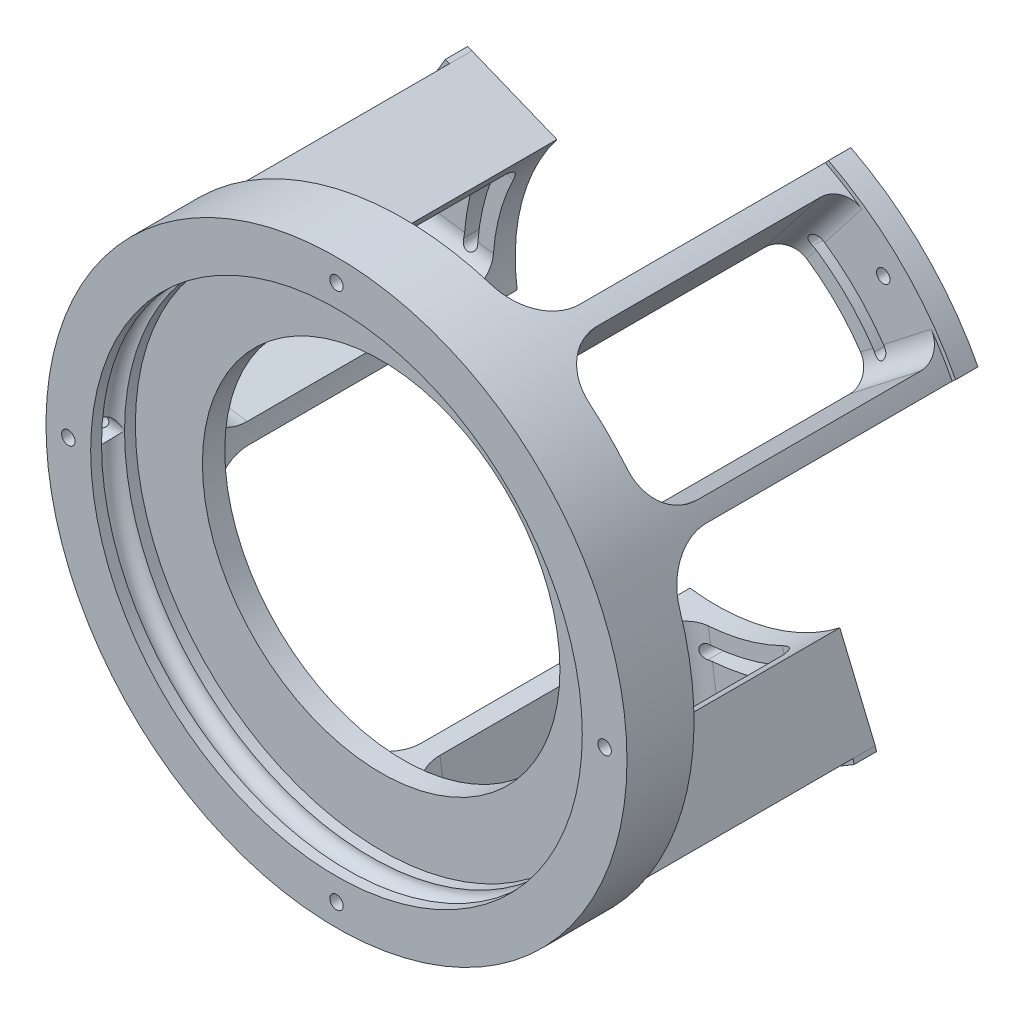
SolidWorks part; units mm, degrees
ref_plane "Alzado" through (0, 0, 0) normal (0, 0, 1) x (1, 0, 0)
ref_plane "Planta" through (0, 0, 0) normal (0, 1, 0) x (1, 0, 0)
ref_plane "Vista lateral" through (0, 0, 0) normal (1, 0, 0) x (0, 0, -1)
sketch "Croquis1" plane through (0, 0, 0) normal (0, 0, 1) x (1, 0, 0)
  circle A0 centre (0, 0) radius 65
  circle A1 centre (0, 0) radius 27.5
  dimension "D1" = 130
  dimension "D5" = 55
extrude "Saliente-Extruir1" add sketch "Croquis1" along normal blind 5
sketch "Croquis2" plane through (0, 0, 5) normal (0, 0, 1) x (1, 0, 0)
  circle A0 centre (0, 0) radius 65
  circle A1 centre (0, 0) radius 55
  dimension "D1" = 130
  dimension "D2" = 10
extrude "Saliente-Extruir2" add sketch "Croquis2" along normal blind 10
sketch "Croquis3" plane through (0, 0, 15) normal (0, 0, 1) x (1, 0, 0)
  line L0 (-73.6289, 0) -> (79.389, 0) construction
  line L1 (0, -78.8882) -> (0, 68.8706) construction
  circle A0 centre (-60, 0) radius 1.5
  circle A1 centre (0, 0) radius 55 construction
  circle A2 centre (0, 60) radius 1.5
  circle A3 centre (60, 0) radius 1.5
  circle A4 centre (0, -60) radius 1.5
  point P19 (0, 0)
  dimension "D1" = 3
  dimension "D2" = 60
  dimension "D3" = 4
extrude "Cortar-Extruir1" cut sketch "Croquis3" against normal blind 10
sketch "Croquis4" plane through (0, 0, 0) normal (0, 0, -1) x (-1, 0, 0)
  line L0 (0, 0) -> (62.7852, 16.8232) construction
  line L1 (0, 0) -> (-16.8232, -62.7852) construction
  line L2 (45.9619, -45.9619) -> (-45.9619, 45.9619) construction
  line L3 (54.6983, 35.1154) -> (18.3812, 20.4544)
  line L4 (-57.76, 29.8125) -> (-26.9046, 5.6914)
  line L5 (-29.3671, 57.9877) -> (-5.6914, 26.9046)
  line L7 (-55.7917, 33.351) -> (-25.6879, 9.8174)
  line L8 (-26.9046, 5.6914) -> (-25.6879, 9.8174)
  line L9 (-5.6914, 26.9046) -> (-9.8174, 25.6879)
  line L10 (-33.351, 55.7917) -> (-9.8174, 25.6879)
  line L11 (56.7786, 31.6416) -> (21.3461, 17.3376)
  line L12 (18.3812, 20.4544) -> (21.3461, 17.3376)
  line L13 (64.9024, -3.5612) -> (26.1458, -8.5234)
  line L14 (64.9925, 0.9869) -> (27.1551, -4.3418)
  line L15 (26.1458, -8.5234) -> (27.1551, -4.3418)
  line L16 (3.0617, -64.9279) -> (8.5234, -26.1458)
  line L17 (-0.9869, -64.9925) -> (4.3418, -27.1551)
  line L18 (8.5234, -26.1458) -> (4.3418, -27.1551)
  line L19 (-35.5353, -54.4265) -> (-20.4544, -18.3812)
  line L20 (-31.6416, -56.7786) -> (-17.3376, -21.3461)
  line L21 (-20.4544, -18.3812) -> (-17.3376, -21.3461)
  line L22 (-0.9869, -64.9925) -> (3.0617, -64.9279)
  line L23 (54.6983, 35.1154) -> (56.7786, 31.6416)
  line L24 (56.7786, 31.6416) -> (57.8313, 30.9786)
  circle A0 centre (0, 0) radius 65 construction
  circle A1 centre (0, 0) radius 27.5 construction
  arc A2 (-29.3671, 57.9877) -> (-33.351, 55.7917) centre (0, 0) ccw
  arc A3 (-55.7917, 33.351) -> (-57.76, 29.8125) centre (0, 0) ccw
  arc A4 (64.9024, -3.5612) -> (64.9925, 0.9869) centre (0, 0) ccw
  arc A5 (-35.5353, -54.4265) -> (-31.6416, -56.7786) centre (0, 0) ccw
  point P38 (0, 0)
  circle M1 centre (0, 0) radius 65
  circle M2 centre (0, 0) radius 27.5
  dimension "D1" = 4
  dimension "D2" = 5.6914
  dimension "D4" = 30
  dimension "D5" = 40
  dimension "D6" = 120
  dimension "D7" = 20
  dimension "D9" = 3
extrude "Saliente-Extruir3" add sketch "Croquis4" along normal blind 70 contours L7 L4 M1 M2 | L10 L5 M1 M2 | L23 L3 L11 M2 | L14 L13 M1 M2 | L20 L19 M1 M2 | L17 L22 L16 M2 region at (-37.8239, 26.1553, 0) region at (19.7989, 41.9217, 0) region at (-46.2047, -3.8145, 0) region at (41.5715, 19.6854, 0) region at (-3.7392, -45.8341, 0) region at (26.4058, -38.1072, 0)
sketch "Croquis5" plane through (0, 0, -70) normal (0, 0, -1) x (-1, 0, 0)
  line L0 (-20.4544, -18.3812) -> (-35.5353, -54.4265)
  line L2 (64.9925, 0.9869) -> (27.1551, -4.3418)
  line L3 (26.1458, -8.5234) -> (64.9024, -3.5612)
  line L4 (3.0617, -64.9279) -> (8.5234, -26.1458)
  line L5 (26.1458, -8.5234) -> (64.9024, -3.5612)
  line L6 (27.1551, -4.3418) -> (64.9925, 0.9869)
  line L7 (56.7786, 31.6416) -> (21.3461, 17.3376)
  line L8 (-5.6914, 26.9046) -> (-29.3671, 57.9877)
  line L9 (54.6983, 35.1154) -> (59.5043, 36.7912)
  line L10 (-57.76, 29.8125) -> (-26.9046, 5.6914)
  line L11 (56.7786, 31.6416) -> (54.6983, 35.1154)
  line L12 (54.6983, 35.1154) -> (18.3812, 20.4544)
  line L13 (21.3461, 17.3376) -> (56.7786, 31.6416)
  line L15 (54.6983, 35.1154) -> (18.3812, 20.4544)
  line L16 (-58.9655, 37.7236) -> (-61.6142, 33.1366)
  line L17 (62.1524, 32.2038) -> (59.5043, 36.7912)
  line L18 (-58.9655, 37.7236) -> (-64.263, 28.5496) construction
  line L19 (-57.76, 29.8125) -> (-61.6142, 33.1366)
  line L20 (-29.3671, 57.9877) -> (-32.9377, 61.7665)
  line L21 (4.2586, 22.0933) -> (-27.8349, 64.2278) construction
  line L22 (-64.263, 28.5496) -> (-22.0566, -4.445) construction
  line L24 (-54.6934, 35.123) -> (-57.76, 29.8125) construction
  line L25 (64.9024, -3.5612) -> (69.9603, -2.3583)
  line L26 (3.0617, -64.9279) -> (2.11, -69.9278)
  line L27 (-3.1869, -69.9274) -> (2.11, -69.9278)
  line L28 (-35.5353, -54.4265) -> (-37.0225, -59.4082)
  arc A0 (-5.6914, 26.9046) -> (18.3812, 20.4544) centre (0, 0) ccw construction
  arc A1 (21.3461, 17.3376) -> (18.3812, 20.4544) centre (0, 0) ccw
  arc A2 (64.9024, -3.5612) -> (64.9925, 0.9869) centre (0, 0) ccw
  arc A3 (26.1458, -8.5234) -> (27.1551, -4.3418) centre (0, 0) ccw
  arc A5 (26.1458, -8.5234) -> (27.1551, -4.3418) centre (0, 0) ccw
  arc A6 (64.9925, 0.9869) -> (56.7786, 31.6416) centre (0, 0) ccw
  arc A7 (27.1551, -4.3418) -> (21.3461, 17.3376) centre (0, 0) ccw
  arc A9 (27.1551, -4.3418) -> (21.3461, 17.3376) centre (0, 0) ccw
  arc A10 (21.3461, 17.3376) -> (18.3812, 20.4544) centre (0, 0) ccw
  arc A13 (-20.4544, -18.3812) -> (-17.3376, -21.3461) centre (0, 0) ccw
  arc A14 (-17.3376, -21.3461) -> (4.3418, -27.1551) centre (0, 0) ccw
  arc A15 (4.3418, -27.1551) -> (8.5234, -26.1458) centre (0, 0) ccw
  arc A17 (26.1458, -8.5234) -> (8.5234, -26.1458) centre (0, 0) ccw construction
  arc A18 (-5.6914, 26.9046) -> (-9.8174, 25.6879) centre (0, 0) ccw
  arc A19 (-9.8174, 25.6879) -> (-25.6879, 9.8174) centre (0, 0) ccw
  arc A20 (-25.6879, 9.8174) -> (-26.9046, 5.6914) centre (0, 0) ccw
  arc A21 (-37.8248, 58.9006) -> (-58.9655, 37.7236) centre (0, 0) ccw
  arc A22 (69.9218, 3.3069) -> (62.1524, 32.2038) centre (0, 0) ccw
  arc A23 (-27.8349, 64.2278) -> (-37.8248, 58.9006) centre (0, 0) ccw construction
  arc A24 (69.9603, -2.3583) -> (69.9218, 3.3069) centre (0, 0) ccw
  arc A25 (-32.9377, 61.7665) -> (-37.8248, 58.9006) centre (0, 0) ccw
  arc A26 (-21.0174, 8.0325) -> (-22.0566, -4.445) centre (0, 0) ccw construction
  arc A27 (-8.0325, 21.0174) -> (-21.0174, 8.0325) centre (0, 0) ccw construction
  arc A28 (4.2586, 22.0933) -> (-8.0325, 21.0174) centre (0, 0) ccw construction
  arc A30 (-35.123, 54.6934) -> (-54.6934, 35.123) centre (0, 0) ccw construction
  arc A31 (-20.4544, -18.3812) -> (-26.9046, 5.6914) centre (0, 0) ccw construction
  arc A32 (-32.097, -62.2076) -> (-3.1869, -69.9274) centre (0, 0) ccw
  arc A33 (-37.0225, -59.4082) -> (-32.097, -62.2076) centre (0, 0) ccw
  arc A35 (-29.3671, 57.9877) -> (-35.123, 54.6934) centre (0, 0) ccw construction
  point P32 (0, 0)
  point P67 (0, 0)
  dimension "D1" = 0
  dimension "D2" = 0
  dimension "D3" = 0
  dimension "D5" = 5
  dimension "D4" = 3
  dimension "D6" = 3
extrude "Saliente-Extruir4" add sketch "Croquis5" against normal blind 5
sketch "Croquis6" plane through (0, 0, -70) normal (0, 0, -1) x (-1, 0, 0)
  circle A0 centre (0, 0) radius 45
  dimension "D1" = 90
extrude "Cortar-Extruir2" cut sketch "Croquis6" against normal up to surface (70 mm away) up to face at (-0.5276, 40.6135, 0)
sketch "Croquis7" plane through (0, 0, 0) normal (0, 0, -1) x (-1, 0, 0)
  line L0 (62.1524, 32.2038) -> (59.5043, 36.7912) construction
  line L1 (62.1524, 32.2038) -> (59.5043, 36.7912)
  line L2 (59.5043, 36.7912) -> (69.9603, -2.3583) construction
  line L3 (0, 0) -> (64.7323, 17.2164) construction
  line L4 (0, 0) -> (-73.786, 74.06) construction
  line L5 (0, 0) -> (-21.6047, -80.0361) construction
  line L6 (0, 0) -> (-81.2841, -21.6186) construction
  line L7 (0, 0) -> (62.4714, -62.7034) construction
  line L8 (0, 0) -> (19.0447, 70.5525) construction
  arc A0 (69.9603, -2.3583) -> (62.1524, 32.2038) centre (0, 0) ccw construction
  arc A1 (69.9603, -2.3583) -> (62.1524, 32.2038) centre (0, 0) ccw
  circle A2 centre (-57.9842, -15.4217) radius 1.5
  arc A3 (-57.76, 29.8125) -> (-35.5353, -54.4265) centre (0, 0) ccw construction
  circle A4 centre (15.6365, 57.9267) radius 1.5
  circle A5 centre (42.3477, -42.505) radius 1.5
  point P21 (0, 0)
  dimension "D2" = 120
  dimension "D3" = 3
  dimension "D4" = 60
  dimension "D5" = 3
  dimension "D1" = 120
extrude "Cortar-Extruir3" cut sketch "Croquis7" against normal blind 5 contours A2 | A5 | A4
sketch "Croquis8" plane through (0, 0, -70) normal (0, 0, -1) x (-1, 0, 0)
  line L0 (0, 0) -> (-65.055, 65.2966) construction
  line L1 (0, 0) -> (89.7663, 23.8746) construction
  line L2 (0, 0) -> (-21.6505, -80.2056) construction
  line L3 (-57.9842, -15.4217) -> (0, 0) construction
  circle A0 centre (-42.3477, 42.505) radius 1.5
  circle A1 centre (57.9842, 15.4217) radius 1.5
  circle A2 centre (-15.6365, -57.9267) radius 1.5
  point P15 (0, 0)
  dimension "D4" = 3
  dimension "D7" = 60
  dimension "D1" = 120
  dimension "D2" = 60
  dimension "D3" = 60
  dimension "D5" = 60
  dimension "D8" = 60
  dimension "D6" = 3
extrude "Cortar-Extruir4" cut sketch "Croquis8" against normal blind 10
sketch "Croquis11" plane through (0, 0, 0) normal (1, 0, 0) x (0, 0, -1)
  line L0 (-15, 55) -> (-5, 55) construction
  line L1 (-15, 55) -> (-15, -55) construction
  line L2 (-15, 65) -> (-15, -65) construction
  line L3 (-5, 55) -> (-5, -55) construction
  line L4 (-51.3174, 0) -> (115.0881, 0) construction
  circle A0 centre (-10, 55) radius 2.575
  dimension "D1" = 5.15
revolve "Cortar-Revolución1" cut sketch "Croquis11" angle 360 about L4
sketch "Croquis12" plane through (0, 0, 0) normal (1, 0, 0) x (0, 0, -1)
  line L0 (-15, 65) -> (-15, -65) construction
  circle A0 centre (-10, 0.0067) radius 2.575
  dimension "D1" = 5.15
  dimension "D2" = 5
extrude "Cortar-Extruir5" cut sketch "Croquis12" against normal blind 100
fillet "Redondeo1" radius 10 12 edges at (-54.9776, -0.4235, 0) (23.1586, 49.8367, 0) (-4.4925, -54.7682, 0) (-0.4235, -54.9776, 0) (27.8555, -47.4002, 0) (31.5806, -44.9743, 0) (-54.7391, -4.8624, 0) (27.122, 47.8237, 0)
fillet "Redondeo2" radius 5 6 edges at (-0.4235, -54.9776, -65) (27.8555, -47.4002, -65) (-54.9776, -0.4235, -65) (-47.4002, 27.8555, -65) (27.122, 47.8237, -65) (47.8237, 27.122, -65)
sketch "Croquis13" plane through (0, 0, -70) normal (0, 0, -1) x (-1, 0, 0)
  circle A0 centre (0, 0) radius 66
  dimension "D1" = 132
extrude "Cortar-Extruir6" cut sketch "Croquis13" against normal blind 10 flip side to cut
sketch "Croquis14" plane through (0, 0, 0) normal (0, 0, -1) x (-1, 0, 0)
  circle A0 centre (0, 0) radius 40
  dimension "D1" = 80
extrude "Cortar-Extruir7" cut sketch "Croquis14" against normal blind 10
sketch "Croquis15" plane through (0, 0, -70) normal (0, 0, -1) x (-1, 0, 0)
  circle A1 centre (0, 0) radius 39.9223 construction
  arc A2 (44.7736, 22.2558) -> (49.9142, 2.9277) centre (0, 0) cw construction
  arc A3 (-41.6609, 27.6472) -> (-27.4926, 41.7631) centre (0, 0) cw construction
  arc A4 (-28.3174, 43.016) -> (-42.9107, 28.4766) centre (0, 0) ccw
  arc A5 (-26.6678, 40.5102) -> (-40.4111, 26.8178) centre (0, 0) ccw
  arc A6 (-18.8334, 46.3174) -> (-46.2152, 19.0828) centre (0, 0) ccw
  arc A7 (-27.4482, 41.7923) -> (-41.6609, 27.6472) centre (0, 0) ccw construction
  arc A8 (-26.6678, 40.5102) -> (-28.3174, 43.016) centre (-27.4926, 41.7631) ccw
  arc A9 (-42.9107, 28.4766) -> (-40.4111, 26.8178) centre (-41.6609, 27.6472) ccw
  arc A10 (51.4116, 3.0155) -> (46.1169, 22.9235) centre (0, 0) ccw
  arc A11 (48.4168, 2.8399) -> (43.4304, 21.5881) centre (0, 0) ccw
  arc A12 (48.4168, 2.8399) -> (51.4116, 3.0155) centre (49.9142, 2.9277) ccw
  arc A13 (46.1169, 22.9235) -> (43.4304, 21.5881) centre (44.7736, 22.2558) ccw
  arc A14 (-3.1127, -49.903) -> (-22.4216, -44.6908) centre (0, 0) cw construction
  arc A15 (-23.0943, -46.0316) -> (-3.2061, -51.4001) centre (0, 0) ccw
  arc A16 (-21.749, -43.3501) -> (-3.0194, -48.4059) centre (0, 0) ccw
  arc A17 (-21.749, -43.3501) -> (-23.0943, -46.0316) centre (-22.4216, -44.6908) ccw
  arc A18 (-3.2061, -51.4001) -> (-3.0194, -48.4059) centre (-3.1127, -49.903) ccw
  point P17 (0.001, 0)
  point P22 (-35.2897, 35.4208)
  point P24 (0, 0)
  point P32 (48.3202, 12.8514)
  point P39 (-13.0305, -48.2722)
  point P44 (0, 0)
  dimension "D2" = 5
  dimension "D4" = 3
  dimension "D1" = 1.5
  dimension "D5" = 20
extrude "Cortar-Extruir8" cut sketch "Croquis15" against normal blind 10
sketch "Croquis17" plane through (0, 0, -70) normal (0, 0, -1) x (-1, 0, 0)
  arc A0 (-27.4926, 41.7631) -> (-41.6609, 27.6472) centre (0, 0) ccw construction
  arc A1 (-27.4926, 41.7631) -> (-41.6609, 27.6472) centre (0, 0) ccw
  arc A2 (49.9142, 2.9277) -> (44.7736, 22.2558) centre (0, 0) ccw
  arc A3 (-22.4216, -44.6908) -> (-3.1127, -49.903) centre (0, 0) ccw
  point P10 (0, 0)
  dimension "D1" = 3
